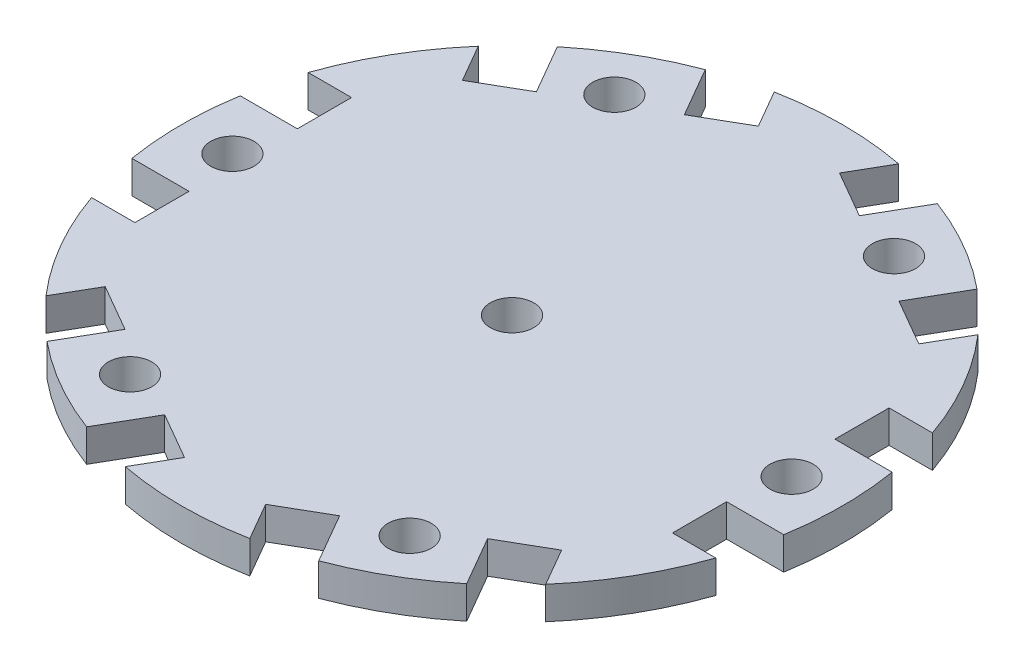
SolidWorks part; units mm, degrees
ref_plane "Alzado" through (0, 0, 0) normal (0, 0, 1) x (1, 0, 0)
ref_plane "Planta" through (0, 0, 0) normal (0, 1, 0) x (1, 0, 0)
ref_plane "Vista lateral" through (0, 0, 0) normal (1, 0, 0) x (0, 0, -1)
sketch "Croquis1" plane through (0, 0, 0) normal (0, 1, 0) x (1, 0, 0)
  circle A0 centre (0, 0) radius 30.5
extrude "Saliente-Extruir1" add sketch "Croquis1" along normal blind 3
sketch "Croquis2" plane through (0, 3, 0) normal (0, 1, 0) x (1, 0, 0)
  circle A0 centre (0, 0) radius 2
extrude "Cortar-Extruir1" cut sketch "Croquis2" against normal blind 4
sketch "Croquis5" plane through (0, 3, 0) normal (0, 1, 0) x (1, 0, 0)
  line L1 (28.8141, -5) -> (30.0874, -5)
  line L2 (28.8141, 5) -> (30.0874, 5)
  line L3 (-24.8141, 10) -> (-28.8141, 10)
  line L4 (24.8141, -5) -> (24.8141, -10)
  line L5 (-24.8141, -10) -> (-28.8141, -10)
  line L6 (24.8141, -5) -> (28.8141, -5)
  line L7 (24.8141, 5) -> (24.8141, 10)
  line L8 (-24.8141, 5) -> (-28.8141, 5)
  line L9 (-24.8141, 5) -> (-24.8141, 10)
  line L10 (-24.8141, -5) -> (-28.8141, -5)
  line L11 (-24.8141, -5) -> (-24.8141, -10)
  line L12 (24.8141, 5) -> (28.8141, 5)
  line L13 (24.8141, -10) -> (28.8141, -10)
  line L14 (24.8141, 10) -> (28.8141, 10)
  line L15 (-28.8141, 5) -> (-30.0874, 5)
  line L16 (-28.8141, -5) -> (-30.0874, -5)
  line L17 (18.7372, 22.4537) -> (19.3738, 23.5564)
  line L18 (-24.8141, 0) -> (-12.407, -21.4896)
  line L19 (-12.407, -21.4896) -> (12.407, -21.4896)
  line L20 (12.407, -21.4896) -> (24.8141, 0)
  line L21 (24.8141, 0) -> (12.407, 21.4896)
  line L22 (12.407, 21.4896) -> (-12.407, 21.4896)
  line L23 (-12.407, 21.4896) -> (-24.8141, 0)
  line L24 (-21.0673, -16.4896) -> (-23.0673, -19.9537)
  line L25 (-3.7468, -26.4896) -> (-5.7468, -29.9537)
  line L26 (-16.7372, -18.9896) -> (-18.7372, -22.4537)
  line L27 (-16.7372, -18.9896) -> (-21.0673, -16.4896)
  line L28 (-8.0769, -23.9896) -> (-10.0769, -27.4537)
  line L29 (-8.0769, -23.9896) -> (-3.7468, -26.4896)
  line L30 (-18.7372, -22.4537) -> (-19.3738, -23.5564)
  line L31 (-10.0769, -27.4537) -> (-10.7136, -28.5564)
  line L32 (10.0769, 27.4537) -> (10.7136, 28.5564)
  line L33 (16.7372, 18.9896) -> (21.0673, 16.4896)
  line L34 (16.7372, 18.9896) -> (18.7372, 22.4537)
  line L35 (8.0769, 23.9896) -> (3.7468, 26.4896)
  line L36 (8.0769, 23.9896) -> (10.0769, 27.4537)
  line L37 (21.0673, 16.4896) -> (23.0673, 19.9537)
  line L38 (3.7468, 26.4896) -> (5.7468, 29.9537)
  line L39 (-3.7468, 26.4896) -> (-5.7468, 29.9537)
  line L40 (-21.0673, 16.4896) -> (-23.0673, 19.9537)
  line L41 (-8.0769, 23.9896) -> (-10.0769, 27.4537)
  line L42 (-8.0769, 23.9896) -> (-3.7468, 26.4896)
  line L43 (-16.7372, 18.9896) -> (-18.7372, 22.4537)
  line L44 (-16.7372, 18.9896) -> (-21.0673, 16.4896)
  line L45 (-10.0769, 27.4537) -> (-10.7136, 28.5564)
  line L46 (-18.7372, 22.4537) -> (-19.3738, 23.5564)
  line L47 (10.0769, -27.4537) -> (10.7136, -28.5564)
  line L48 (18.7372, -22.4537) -> (19.3738, -23.5564)
  line L49 (8.0769, -23.9896) -> (3.7468, -26.4896)
  line L50 (8.0769, -23.9896) -> (10.0769, -27.4537)
  line L51 (16.7372, -18.9896) -> (21.0673, -16.4896)
  line L52 (16.7372, -18.9896) -> (18.7372, -22.4537)
  line L53 (3.7468, -26.4896) -> (5.7468, -29.9537)
  line L54 (21.0673, -16.4896) -> (23.0673, -19.9537)
  circle A0 centre (0, 0) radius 21.4896 construction
  circle A1 centre (0, 0) radius 30.5 construction
  arc A2 (-28.8141, 10) -> (-30.0874, 5) centre (0, 0) ccw
  arc A3 (-5.7468, 29.9537) -> (-10.7136, 28.5564) centre (0, 0) ccw
  arc A4 (-30.0874, -5) -> (-28.8141, -10) centre (0, 0) ccw
  arc A5 (30.0874, -5) -> (28.8141, -10) centre (0, 0) cw
  arc A6 (28.8141, 10) -> (30.0874, 5) centre (0, 0) cw
  arc A7 (-23.0673, -19.9537) -> (-19.3738, -23.5564) centre (0, 0) ccw
  arc A8 (-10.7136, -28.5564) -> (-5.7468, -29.9537) centre (0, 0) ccw
  arc A9 (-19.3738, 23.5564) -> (-23.0673, 19.9537) centre (0, 0) ccw
  arc A10 (19.3738, 23.5564) -> (23.0673, 19.9537) centre (0, 0) cw
  arc A11 (5.7468, 29.9537) -> (10.7136, 28.5564) centre (0, 0) cw
  arc A12 (10.7136, -28.5564) -> (5.7468, -29.9537) centre (0, 0) cw
  arc A13 (23.0673, -19.9537) -> (19.3738, -23.5564) centre (0, 0) cw
  circle M2 centre (0, 0) radius 30.5
extrude "Cortar-Extruir3" cut sketch "Croquis5" against normal blind 4 contours L15 L8 L9 L3 M2 | L14 L7 L12 L2 M2 | L4 L13 L1 L6 M2 | L54 L51 L52 L48 M2 | L49 L53 L47 L50 M2 | L28 L31 L25 L29 M2 | L30 L26 L27 L24 M2 | L10 L16 L5 L11 M2 | L43 L46 L40 L44 M2 | L45 L41 L42 L39 M2 | L38 L35 L36 L32 M2 | L33 L37 L17 L34 M2 region at (27.1844, 3, 7.3876) region at (19.99, 3, 19.8486) region at (27.1844, 3, -7.3876) region at (7.1944, 3, 27.2362) region at (19.99, 3, -19.8486) region at (-7.1944, 3, 27.2362) region at (7.1944, 3, -27.2362) region at (-19.99, 3, 19.8486) region at (-7.1944, 3, -27.2362) region at (-27.1844, 3, 7.3876) region at (-19.99, 3, -19.8486) region at (-27.1844, 3, -7.3876)
sketch "Croquis7" plane through (0, 3, 0) normal (0, 1, 0) x (1, 0, 0)
  line L2 (25.8141, 0) -> (12.907, 22.3556)
  line L3 (12.907, 22.3556) -> (-12.907, 22.3556)
  line L4 (-12.907, 22.3556) -> (-25.8141, 0)
  line L5 (-25.8141, 0) -> (-12.907, -22.3556)
  line L6 (-12.907, -22.3556) -> (12.907, -22.3556)
  line L7 (12.907, -22.3556) -> (25.8141, 0)
  circle A0 centre (25.8141, 0) radius 2
  circle A4 centre (-25.8141, 0) radius 2
  circle A5 centre (0, 0) radius 22.3556 construction
  circle A6 centre (12.907, 22.3556) radius 2
  circle A7 centre (-12.907, -22.3556) radius 2
  circle A8 centre (-12.907, 22.3556) radius 2
  circle A9 centre (12.907, -22.3556) radius 2
extrude "Cortar-Extruir4" cut sketch "Croquis7" against normal blind 10 contours A8 L4 L3 | A4 L4 L5 | A4 L5 L4 | A8 L3 L4 | L2 A6 L3 | L3 A6 L2 | L7 A0 L2 | L2 A0 L7 | A7 L5 L6 | A7 L6 L5 | L6 A9 L7 | L7 A9 L6 | A4 region at (24.7114, 3, 0) region at (26.3654, 3, 0) region at (12.3557, 3, -21.4007) region at (13.1827, 3, -22.8331) region at (13.1827, 3, 22.8331) region at (12.3557, 3, 21.4007) region at (-12.3557, 3, -21.4007) region at (-13.1827, 3, -22.8331) region at (-13.1827, 3, 22.8331) region at (-12.3557, 3, 21.4007) region at (-24.7114, 3, 0) region at (-26.3654, 3, 0)
